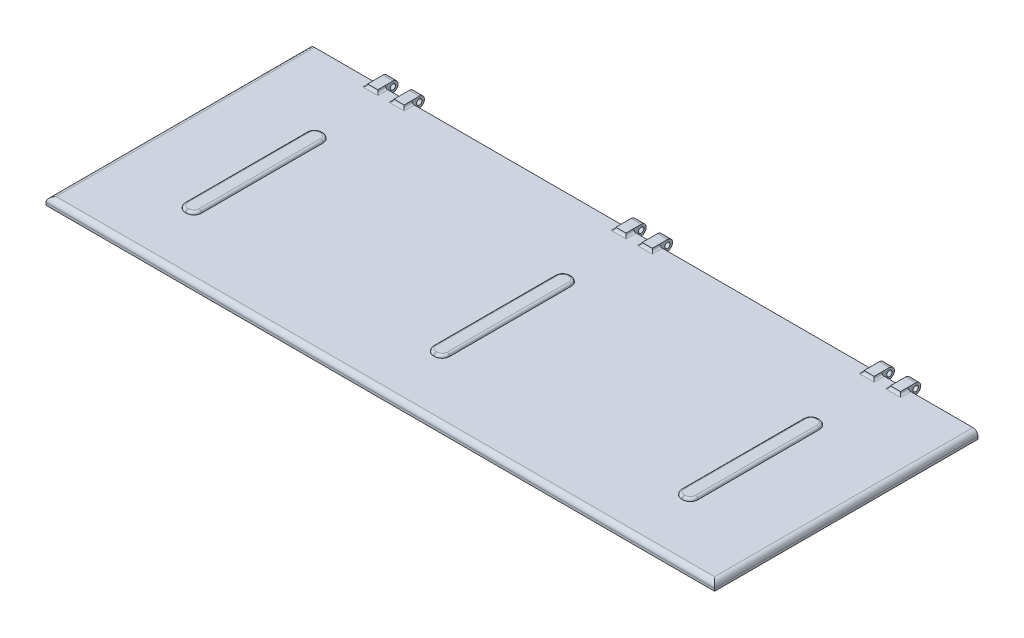
SolidWorks part; units mm, degrees
material "PC Wysoka lepkość"
ref_plane "Płaszczyzna przednia" through (0, 0, 0) normal (0, 0, 1) x (1, 0, 0)
ref_plane "Płaszczyzna górna" through (0, 0, 0) normal (0, 1, 0) x (1, 0, 0)
ref_plane "Płaszczyzna prawa" through (0, 0, 0) normal (1, 0, 0) x (0, 0, -1)
sketch "Szkic1" plane through (0, 0, 0) normal (0, 1, 0) x (1, 0, 0)
  line L1 (-660, 260) -> (660, 260)
  line L2 (-660, 260) -> (-660, -260)
  line L3 (-660, -260) -> (660, -260)
  line L4 (660, 260) -> (660, -260)
  point P4 (0, 260)
  point P6 (-660, 0)
  dimension "D1" = 1320
  dimension "D2" = 520
extrude "Dodanie-wyciągnięcie1" add sketch "Szkic1" along normal blind 15
sketch "Szkic3" plane through (0, 0, 0) normal (0, -1, 0) x (1, 0, 0)
  line L0 (-660, -260) -> (-660, 260) construction
  line L1 (-530, -245) -> (-510, -245)
  line L2 (-530, -245) -> (-530, -285)
  line L3 (-530, -285) -> (-510, -285)
  line L4 (-510, -245) -> (-510, -285)
  line L5 (-478, -245) -> (-458, -245)
  line L6 (-478, -245) -> (-478, -285)
  line L7 (-478, -285) -> (-458, -285)
  line L8 (-458, -245) -> (-458, -285)
  line L9 (660, -260) -> (-660, -260) construction
  line L10 (-660, 260) -> (660, 260) construction
  line L11 (-495, -120) -> (-493, -120)
  line L12 (-510, -105) -> (-510, 135)
  line L13 (-495, 150) -> (-493, 150)
  line L14 (-478, -105) -> (-478, 135)
  arc A0 (-510, 135) -> (-495, 150) centre (-495, 135) cw
  arc A1 (-493, 150) -> (-478, 135) centre (-493, 135) cw
  arc A2 (-493, -120) -> (-478, -105) centre (-493, -105) ccw
  arc A3 (-495, -120) -> (-510, -105) centre (-495, -105) cw
  point P22 (-478, 150)
  point P25 (-478, -120)
  dimension "D9" = 15
  dimension "D1" = 32
  dimension "D2" = 130
  dimension "D3" = 20
  dimension "D4" = 20
  dimension "D5" = 15
  dimension "D6" = 25
  dimension "D7" = 110
  dimension "D8" = 270
extrude "Dodanie-wyciągnięcie2" add sketch "Szkic3" against normal blind 20
fillet "Zaokrąglenie1" 2 edges at (-468, 20, -285) (-468, 0, -285) type full round first side face at (-468, 20, -265) second side face at (-329.3333, 0, -181.6667) middle face at (-468, 10, -285)
fillet "Zaokrąglenie2" 2 edges at (-520, 20, -285) (-520, 0, -285) type full round first side face at (-520, 20, -265) second side face at (-329.3333, 0, -180) middle face at (-520, 10, -285)
sketch "Szkic4" plane through (-530, 0, 0) normal (-1, 0, 0) x (0, 0, 1)
  circle A0 centre (-275, 10) radius 5.25
  dimension "D1" = 10.5
extrude "Wytnij-wyciągnięcie1" cut sketch "Szkic4" against normal up to surface (72 mm away) up to face at (-458, 11.6667, -261.6667)
fillet "Zaokrąglenie5" radius 5 6 edges at (-458, 15, -252.5) (-478, 15, -252.5) (-468, 15, -245) (-510, 15, -252.5) (-520, 15, -245) (-530, 15, -252.5)
fillet "Zaokrąglenie9" radius 5 8 edges at (-505.6066, 20, 145.6066) (-494, 20, 150) (-482.3934, 20, 145.6066) (-478, 20, 15) (-482.3934, 20, -115.6066) (-494, 20, -120) (-505.6066, 20, -115.6066) (-510, 20, 15)
sketch "Szkic5" plane through (0, 0, 0) normal (0, -1, 0) x (1, 0, 0)
  line L0 (-495, 145) -> (-493, 145) construction
  line L1 (-483, 135) -> (-483, -105) construction
  line L2 (-493, -115) -> (-495, -115) construction
  line L3 (-505, -105) -> (-505, 135) construction
  line L4 (-495, 145) -> (-493, 145)
  line L5 (-483, 135) -> (-483, -105)
  line L6 (-493, -115) -> (-495, -115)
  line L7 (-505, -105) -> (-505, 135)
  arc A0 (-483, 135) -> (-493, 145) centre (-493, 135) ccw construction
  arc A1 (-495, 145) -> (-505, 135) centre (-495, 135) ccw construction
  arc A2 (-493, -115) -> (-483, -105) centre (-493, -105) ccw construction
  arc A3 (-505, -105) -> (-495, -115) centre (-495, -105) ccw construction
  arc A4 (-483, 135) -> (-493, 145) centre (-493, 135) ccw
  arc A5 (-495, 145) -> (-505, 135) centre (-495, 135) ccw
  arc A6 (-493, -115) -> (-483, -105) centre (-493, -105) ccw
  arc A7 (-505, -105) -> (-495, -115) centre (-495, -105) ccw
extrude "Wytnij-wyciągnięcie2" cut sketch "Szkic5" against normal blind 5
pattern_linear "Szyk liniowy1" count 3 spacing 490 along (1, 0, 0) of "Dodanie-wyciągnięcie2", "Zaokrąglenie1", "Zaokrąglenie2", "Wytnij-wyciągnięcie1", "Zaokrąglenie5", "Zaokrąglenie9", "Wytnij-wyciągnięcie2"
fillet "Zaokrąglenie4" radius 10 3 edges at (660, 15, 0) (0, 15, 260) (-660, 15, 0)
fillet "Zaokrąglenie10" radius 5 24 edges at (494.0711, 5, -112.0711) (486, 5, -115) (477.9289, 5, -112.0711) (475, 5, 15) (477.9289, 5, 142.0711) (486, 5, 145) (494.0711, 5, 142.0711) (4.0711, 5, -112.0711) (-4, 5, -115) (-12.0711, 5, -112.0711) (-15, 5, 15) (-12.0711, 5, 142.0711) (-4, 5, 145) (4.0711, 5, 142.0711) (-485.9289, 5, -112.0711) (-494, 5, -115) (-502.0711, 5, -112.0711) (-505, 5, 15) (-502.0711, 5, 142.0711) (-494, 5, 145) (-485.9289, 5, 142.0711) (497, 5, 15) (7, 5, 15) (-483, 5, 15)
